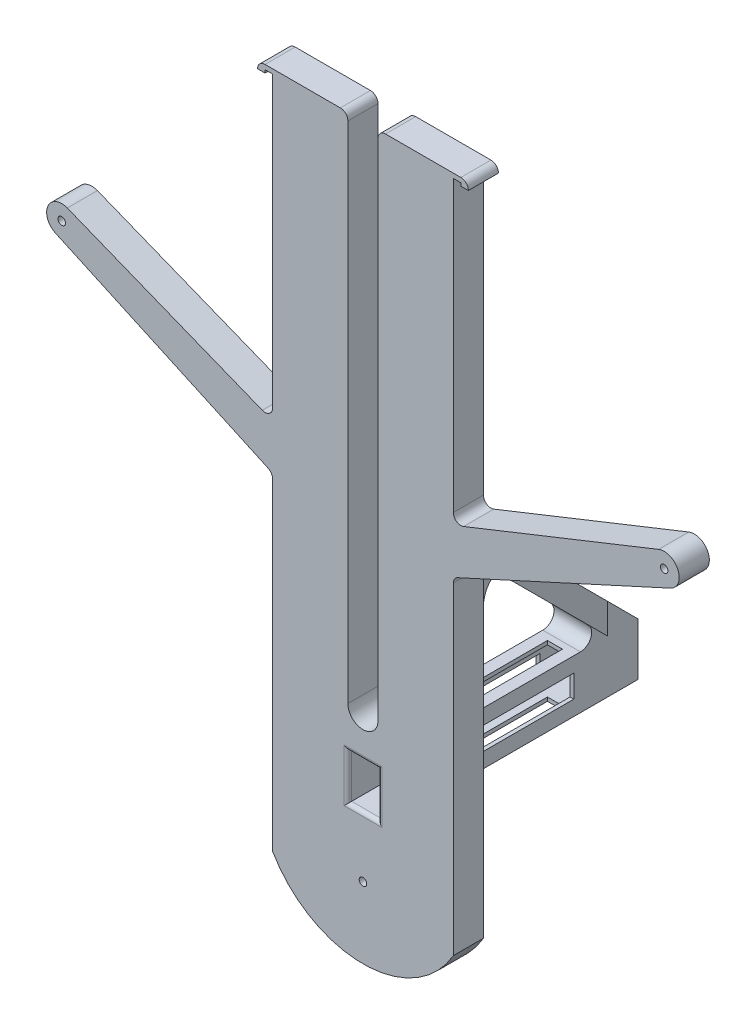
SolidWorks part; units mm, degrees
ref_plane "前视基准面" through (0, 0, 0) normal (0, 0, 1) x (1, 0, 0)
ref_plane "上视基准面" through (0, 0, 0) normal (0, 1, 0) x (1, 0, 0)
ref_plane "右视基准面" through (0, 0, 0) normal (1, 0, 0) x (0, 0, -1)
other "Configuration Table"
sketch "草图1" plane through (0, 0, 0) normal (0, 0, 1) x (1, 0, 0)
  line L1 (-12, 0) -> (-12, 89.4)
  line L2 (-12, 90) -> (-2, 90)
  line L3 (0, -1000) -> (0, -6.9397) construction
  line L4 (12, 0) -> (12, 89.4)
  line L5 (-2, 90) -> (-2, 22)
  line L6 (2, 90) -> (2, 22)
  line L7 (2, 90) -> (12, 90)
  line L8 (0, 90) -> (0, 49000) construction
  line L9 (0, 0) -> (0, 20) construction
  line L10 (12, 90) -> (14, 90)
  line L11 (14, 90) -> (14, 89)
  line L12 (14, 89) -> (13, 89)
  line L13 (13, 89) -> (13, 89.4)
  line L14 (13, 89.4) -> (12, 89.4)
  line L15 (-13, 89) -> (-13, 89.4)
  line L16 (-13, 89.4) -> (-12, 89.4)
  line L17 (-14, 89) -> (-13, 89)
  line L18 (-14, 90) -> (-14, 89)
  line L19 (-12, 90) -> (-14, 90)
  line L20 (2, 10.5) -> (-2, 10.5)
  line L21 (-2, 10.5) -> (-2, 16.5)
  line L22 (-2, 16.5) -> (2, 16.5)
  line L23 (2, 10.5) -> (2, 16.5)
  arc A1 (-2, 22) -> (2, 22) centre (0, 22) ccw
  arc A3 (-12, 0) -> (12, 0) centre (0, 6.9052) ccw
  circle A4 centre (0, 2.5) radius 0.5
  point P8 (0, 0)
  point P9 (0, 90)
  point P36 (0, 10.5)
  point P37 (0, 16.5)
  dimension "D6" = 4
  dimension "D10" = 1
  dimension "D1" = 12
  dimension "D2" = 90
  dimension "D3" = 2
  dimension "D4" = 2
  dimension "D5" = 68
  dimension "D7" = 1
  dimension "D8" = 1
  dimension "D9" = 0.4
  dimension "D11" = 2.5
  dimension "D12" = 2
  dimension "D13" = 6
  dimension "D14" = 14
extrude "凸台-拉伸1" add sketch "草图1" along normal blind 4
fillet "圆角1" radius 1 2 edges at (-14, 90, 2) (14, 90, 2)
fillet "圆角2" radius 1 2 edges at (-2, 90, 2) (2, 90, 2)
sketch "草图2" plane through (0, 0, 0) normal (1, 0, 0) x (0, 0, -1)
  line L0 (-1000, 0) -> (49000, 0) construction
  line L1 (-981.4127, 13.5) -> (49018.5873, 13.5) construction
  line L2 (30, 13.5) -> (30, 17)
  line L3 (30, 13.5) -> (30, 10)
  line L4 (30, 10) -> (0, 10)
  line L5 (0, 0) -> (0, 89.4) construction
  line L6 (30, 17) -> (0, 47)
  line L7 (0, 47) -> (0, 10)
  dimension "D1" = 13.5
  dimension "D2" = 3.5
  dimension "D3" = 3.5
  dimension "D4" = 30
  dimension "D5" = 30
extrude "凸台-拉伸2" add sketch "草图2" along normal mid plane 24
sketch "草图3" plane through (12, 0, 0) normal (1, 0, 0) x (0, 0, -1)
  line L0 (30, 10) -> (26, 10)
  line L1 (0, 10) -> (30, 10) construction
  line L2 (0, -1000) -> (0, 49000) construction
  line L3 (26, 10) -> (26, 17)
  line L4 (26, 17) -> (0, 43)
  line L5 (0, 47) -> (30, 17)
  line L6 (0, 43) -> (0, 10)
  line L7 (0, 10) -> (26, 10)
  line M8 (0, 10) -> (30, 10)
  dimension "D1" = 4
  dimension "D2" = 7
extrude "切除-拉伸1" cut sketch "草图3" against normal blind 24 contours L4 L6 L3 M8 region at (12, 21.4083, -10.1833)
sketch "草图4" plane through (0, 0, -30) normal (0, 0, -1) x (-1, 0, 0)
  line L0 (0, -1000) -> (0, 49000) construction
  line L1 (0, 17) -> (-2.5, 17)
  line L2 (-12, 17) -> (12, 17) construction
  line L3 (-2.5, 17) -> (-2.5, 10)
  line L4 (-12, 10) -> (12, 10) construction
  line L5 (-2.5, 10) -> (0, 10)
  line L6 (-2.5, 17) -> (-12, 17)
  line L7 (-12, 17) -> (-12, 10)
  line L8 (-12, 10) -> (-2.5, 10)
  line L9 (12, 17) -> (12, 10)
  line L10 (2.5, 17) -> (2.5, 10)
  line L11 (2.5, 17) -> (12, 17)
  line L12 (12, 10) -> (2.5, 10)
  line M6 (12, 10) -> (12, 17)
  line M7 (12, 17) -> (-12, 17)
  line M8 (-12, 17) -> (-12, 10)
  line M9 (-12, 10) -> (12, 10)
  dimension "D1" = 2.5
extrude "切除-拉伸2" cut sketch "草图4" against normal blind 24 contours L3 M7 M8 M9 | L10 M7 M9 M6 region at (7.25, 13.5, -30) region at (-7.25, 13.5, -30)
sketch "草图5" plane through (0, 10, 0) normal (0, -1, 0) x (1, 0, 0)
  line L0 (-2.5, -26) -> (-12, 0)
  line L1 (-12, 0) -> (-7, 0)
  line L2 (-12, 0) -> (-2, 0) construction
  line L3 (-7, 0) -> (2.5, -26)
  line L4 (2.5, -26) -> (12, 0)
  line L5 (12, 0) -> (7, 0)
  line L6 (2, 0) -> (12, 0) construction
  line L7 (7, 0) -> (-2.5, -26)
  line L8 (-12, 0) -> (-12, -30)
  line L9 (-12, -30) -> (-2.5, -30)
  line L10 (-2.5, -30) -> (-2.5, -26)
  line L11 (2.5, -26) -> (2.5, -30)
  line L12 (2.5, -30) -> (12, -30)
  line L13 (12, -30) -> (12, 0)
  line L14 (-7, 0) -> (7, 0)
  line M3 (2.5, -30) -> (2.5, -26)
  line M5 (-2.5, -26) -> (-2.5, -30)
  dimension "D1" = 5
  dimension "D2" = 5
extrude "切除-拉伸3" cut sketch "草图5" against normal blind 50 contours L14 L3 L7 | L8 L9 L0 M5 | L12 L13 L4 M3 region at (-8.4608, 10, -19.8431) region at (0, 10, -6.386) region at (8.4608, 10, -19.8431)
sketch "草图6" plane through (0, 0, -30) normal (0, 0, -1) x (-1, 0, 0)
  line L0 (2.5, 13.5) -> (-4.4619, 13.5) construction
  line L1 (2.5, 17) -> (2.5, 10) construction
  line L2 (0, 17) -> (0, 9.8585) construction
  line L3 (-2.5, 17) -> (2.5, 17) construction
  line L5 (-2, 10.5) -> (2, 10.5)
  line L6 (-2, 10.5) -> (-2, 16.5)
  line L7 (-2, 16.5) -> (2, 16.5)
  line L8 (2, 10.5) -> (2, 16.5)
  line L9 (-2, 10.5) -> (2, 16.5) construction
  line L10 (-2, 16.5) -> (2, 10.5) construction
  point P9 (0, 13.5)
  dimension "D1" = 6
  dimension "D2" = 4
extrude "切除-拉伸4" cut sketch "草图6" against normal blind 50
sketch "草图7" plane through (0, 0, 0) normal (0, 0, -1) x (-1, 0, 0)
  circle A0 centre (0, 2.5) radius 1
  circle A1 centre (0, 2.5) radius 0.5
  dimension "D1" = 2
  dimension "D2" = 1
extrude "凸台-拉伸3" add sketch "草图7" along normal blind 3
fillet "圆角3" radius 2 1 edges at (1, 2.5, 0)
fillet "圆角4" radius 0.5 2 edges at (-9.5, 47, 0) (9.5, 47, 0)
sketch "草图9" plane through (0, 0, 4) normal (0, 0, 1) x (1, 0, 0)
  line L0 (-998, 13.5) -> (49002, 13.5) construction
  line L1 (2, 10.5) -> (2, 16.5) construction
  line L2 (0, -983.5) -> (0, 49016.5) construction
  line L3 (2, 16.5) -> (-2, 16.5) construction
  line L4 (39.2599, 60.358) -> (12, 49.5)
  line L5 (12, 0) -> (12, 89.4) construction
  line L6 (40.8316, 56.6811) -> (12, 43.5)
  line L7 (12, 43.5) -> (12, 49.5)
  line L10 (-40.8316, 56.6811) -> (-12, 43.5)
  line L11 (-39.2599, 60.358) -> (-12, 49.5)
  line L12 (-12, 43.5) -> (-12, 49.5)
  arc A0 (40.8316, 56.6811) -> (39.2599, 60.358) centre (40, 58.5) ccw
  circle A1 centre (40, 58.5) radius 0.5
  arc A2 (-40.8316, 56.6811) -> (-39.2599, 60.358) centre (-40, 58.5) cw
  circle A3 centre (-40, 58.5) radius 0.5
  point P5 (2, 13.5)
  point P10 (0, 16.5)
  dimension "D3" = 4
  dimension "D6" = 1
  dimension "D1" = 45
  dimension "D2" = 40
  dimension "D4" = 6
  dimension "D5" = 30
extrude "凸台-拉伸4" add sketch "草图9" against normal blind 4
fillet "圆角5" radius 1 4 edges at (-12, 49.5, 2) (-12, 43.5, 2) (12, 43.5, 2) (12, 49.5, 2)
fillet "圆角6" radius 2 2 edges at (-9.5, 43, 0) (9.5, 43, 0)
sketch "草图10" plane through (0, 0, -30) normal (0, 0, -1) x (-1, 0, 0)
  line L0 (-2.5, 17) -> (-2.5, 10)
  line L1 (-2.5, 17) -> (2.5, 17)
  line L2 (2.5, 17) -> (2.5, 10)
  line L3 (-2.5, 10) -> (2.5, 10) construction
  line L4 (2.5, 17) -> (2.5, 10) construction
  line L5 (2.5, 10) -> (-2.5, 10)
  line L6 (-2, 16.5) -> (2, 16.5)
  line L7 (2, 16.5) -> (2, 10.5)
  line L8 (2, 10.5) -> (-2, 10.5)
  line L9 (-2, 10.5) -> (-2, 16.5)
extrude "凸台-拉伸5" add sketch "草图10" against normal blind 30
fillet "圆角7" radius 1.5 1 edges at (0, 17, -26)
sketch "草图11" plane through (2.5, 0, 0) normal (1, 0, 0) x (0, 0, -1)
  line L0 (-1000, 13.5) -> (49000, 13.5) construction
  line L1 (0, 17) -> (0, 10) construction
  line L3 (2.5, 15) -> (21.5, 15)
  line L4 (2.5, 15) -> (2.5, 12)
  line L5 (2.5, 12) -> (21.5, 12)
  line L6 (21.5, 15) -> (21.5, 12)
  line L7 (2.5, 15) -> (21.5, 12) construction
  line L8 (2.5, 12) -> (21.5, 15) construction
  point P1 (12, 13.5)
  point P5 (0, 13.5)
  dimension "D1" = 12
  dimension "D2" = 19
  dimension "D3" = 3
extrude "切除-拉伸5" cut sketch "草图11" against normal blind 30
sketch "草图12" plane through (0, 10, 0) normal (0, -1, 0) x (1, 0, 0)
  line L0 (0, -1000) -> (0, 49000) construction
  line L2 (-1, -21.5) -> (1, -21.5)
  line L3 (-1, -21.5) -> (-1, -2.5)
  line L4 (-1, -2.5) -> (1, -2.5)
  line L5 (1, -21.5) -> (1, -2.5)
  line L6 (-1, -21.5) -> (1, -2.5) construction
  line L7 (-1, -2.5) -> (1, -21.5) construction
  point P1 (0, -12)
  dimension "D1" = 12
  dimension "D2" = 19
  dimension "D3" = 2
extrude "切除-拉伸6" cut sketch "草图12" against normal blind 8
fillet "圆角8" radius 0.5 8 edges at (0, 10.5, 4) (-2, 13.5, 4) (2, 13.5, 4) (0, 16.5, 4) (0, 10.5, -30) (2, 13.5, -30) (-2, 13.5, -30) (0, 16.5, -30)
fillet "圆角9" radius 0.5 4 edges at (0, 17, 0) (-2.5, 13.5, 0) (0, 10, 0) (2.5, 13.5, 0)
